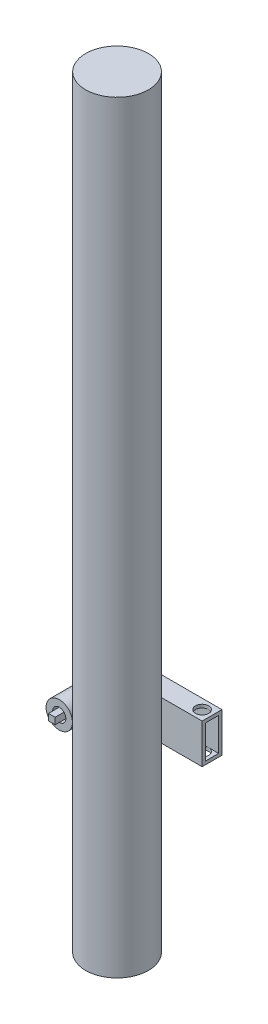
SolidWorks part; units mm, degrees
ref_plane "Front Plane" through (0, 0, 0) normal (0, 0, 1) x (1, 0, 0)
ref_plane "Top Plane" through (0, 0, 0) normal (0, 1, 0) x (1, 0, 0)
ref_plane "Right Plane" through (0, 0, 0) normal (1, 0, 0) x (0, 0, -1)
sketch "Elevation Bar" plane through (0, 0, 0) normal (0, 1, 0) x (1, 0, 0)
  circle A0 centre (0, 0) radius 30.226
  dimension "D1" = 60.452
extrude "Elevation Bar Part" add sketch "Elevation Bar" along normal blind 734.06
sketch "Pole and Drivetrain Pos" plane through (0, 0, 0) normal (0, 0, 1) x (1, 0, 0)
  line L0 (0, 0) -> (172.1794, 0) construction
  line L1 (-30.226, 0) -> (-30.226, 734.06) construction
  line L2 (-30.226, 734.06) -> (30.226, 734.06) construction
  line L3 (30.226, 734.06) -> (30.226, 0) construction
  line L4 (30.226, 0) -> (30.226, 734.06) construction
  line L5 (636.651, 40.7185) -> (27.051, 40.7185) construction
  line L6 (636.651, 53.4185) -> (27.051, 53.4185)
  line L7 (636.651, 53.4185) -> (636.651, 28.0185)
  line L8 (636.651, 28.0185) -> (27.051, 28.0185)
  line L9 (27.051, 53.4185) -> (27.051, 28.0185)
  line L10 (-30.226, 93.98) -> (30.226, 93.98) construction
  line L11 (33.2486, 0) -> (-33.2486, 0) construction
  line L12 (30.226, 185.42) -> (-30.226, 185.42) construction
  line L13 (30.226, 276.86) -> (-30.226, 276.86) construction
  line L14 (30.226, 368.3) -> (-30.226, 368.3) construction
  line L15 (30.226, 459.74) -> (-30.226, 459.74) construction
  line L16 (30.226, 551.18) -> (-30.226, 551.18) construction
  line L17 (30.226, 642.62) -> (-30.226, 642.62) construction
  line L18 (30.226, 73.152) -> (750.8896, 73.152) construction
  circle A0 centre (576.5632, 40.7185) radius 41.275 construction
  circle A1 centre (87.1388, 40.7185) radius 41.275 construction
  circle A2 centre (331.851, 40.7185) radius 41.275 construction
  point P24 (331.851, 40.7185)
  dimension "D2" = 82.55
  dimension "D1" = 609.6
  dimension "D3" = 25.4
  dimension "D4" = 244.7122
  dimension "D5" = 244.7122
  dimension "D6" = 93.98
  dimension "D7" = 185.42
  dimension "D8" = 276.86
  dimension "D9" = 368.3
  dimension "D10" = 459.74
  dimension "D11" = 551.18
  dimension "D12" = 642.62
  dimension "D13" = 73.152
sketch "Driving Wheels Geo" plane through (0, 0, 0) normal (0, 0, 1) x (1, 0, 0)
  line L0 (-30.226, 182.88) -> (-30.226, 101.727) construction
  line L1 (55.626, 101.727) -> (30.226, 101.727) construction
  line L2 (-30.226, 0) -> (-30.226, 734.06) construction
  line L3 (30.226, 734.06) -> (30.226, 0) construction
  line L5 (30.226, 101.727) -> (-30.226, 101.727) construction
  line L6 (-30.226, 182.88) -> (30.226, 101.727) construction
  line L7 (31.8135, 101.727) -> (-30.226, 182.88) construction
  line L8 (30.226, 226.8605) -> (203.668, 53.4185) construction
  line L9 (-42.926, 195.58) -> (44.3164, 195.58) construction
  line L10 (30.226, 73.152) -> (750.8896, 73.152) construction
  line L11 (636.651, 53.4185) -> (27.051, 53.4185) construction
  line L14 (-42.926, 170.18) -> (44.3164, 170.18) construction
  line L15 (44.3164, 170.18) -> (44.3164, 195.58) construction
  line L17 (31.6164, 195.58) -> (57.0164, 195.58) construction
  line L18 (31.6164, 195.58) -> (31.6164, 170.18) construction
  line L19 (31.6164, 170.18) -> (57.0164, 170.18) construction
  line L20 (57.0164, 195.58) -> (57.0164, 170.18) construction
  line L21 (31.6164, 195.58) -> (57.0164, 170.18) construction
  line L22 (31.6164, 170.18) -> (57.0164, 195.58) construction
  circle A1 centre (55.626, 101.727) radius 25.4
  circle A3 centre (-42.926, 182.88) radius 12.7
  circle A4 centre (81.026, 104.2185) radius 50.8 construction
  circle A5 centre (55.626, 101.727) radius 23.8125 construction
  point P28 (44.3164, 182.88)
  dimension "D1" = 50.8
  dimension "D2" = 1.5875
  dimension "D3" = 52.603
  dimension "D4" = 3.175
  dimension "D5" = 182.88
  dimension "D8" = 101.6
  dimension "D6" = 25.4
  dimension "D13" = 3.175
  dimension "D7" = 81.153
  dimension "D9" = 45
  dimension "D10" = 53.317
  dimension "D11" = 25.4
  dimension "D12" = 48.3085
ref_plane "Plane1" through (0, 182.88, 0) normal (0, 1, 0) x (1, 0, 0)
sketch "Clamp Geo" plane through (0, 182.88, 0) normal (0, 1, 0) x (1, 0, 0)
  line L0 (-42.926, -19.8438) -> (-42.926, 50.8635) construction
  line L3 (27.051, 228.6) -> (27.051, -228.6) construction
  line L4 (50.0464, 31.8135) -> (-49.276, 31.8135)
  line L5 (50.0464, 31.8135) -> (50.0464, 50.8635)
  line L6 (50.0464, 50.8635) -> (-49.276, 50.8635)
  line L7 (-49.276, 31.8135) -> (-49.276, 50.8635)
  line L10 (-46.101, 50.8635) -> (-39.751, 50.8635)
  line L11 (-46.101, 50.8635) -> (-46.101, -19.8438)
  line L12 (-46.101, -19.8438) -> (-39.751, -19.8438)
  line L13 (-39.751, 50.8635) -> (-39.751, -19.8438)
  line L14 (-55.626, 12.7) -> (-30.226, 12.7) construction
  line L15 (-55.626, 12.7) -> (-55.626, -12.7) construction
  line L16 (-55.626, -12.7) -> (-30.226, -12.7) construction
  line L17 (-30.226, 12.7) -> (-30.226, -12.7) construction
  line L18 (-55.626, 12.7) -> (-30.226, -12.7) construction
  line L19 (-55.626, -12.7) -> (-30.226, 12.7) construction
  line L20 (0, -30.226) -> (0, 30.226) construction
  line L21 (-30.226, 0) -> (30.226, 0) construction
  line L22 (-46.101, 46.101) -> (-42.926, 46.101) construction
  line L23 (-39.751, 41.3385) -> (-46.101, 41.3385)
  line L24 (-46.101, 41.3385) -> (-46.101, 50.8635) construction
  line L25 (-39.751, 31.8135) -> (-39.751, 50.8635) construction
  line L26 (50.0464, 41.3385) -> (40.5214, 41.3385) construction
  circle A0 centre (0, 0) radius 30.226 construction
  circle A3 centre (-42.926, 46.101) radius 1.8288
  circle A5 centre (-42.926, 36.576) radius 1.8288
  circle A6 centre (40.5214, 41.3385) radius 6.35
  circle A7 centre (40.5214, 41.3385) radius 13.4704 construction
  point P14 (-42.926, 0)
  point P32 (-39.751, 41.3385)
  point P34 (-46.101, 41.3385)
  point P36 (-42.926, 41.3385)
  point P42 (50.0464, 41.3385)
  dimension "D1" = 60.452
  dimension "D4" = 1.5875
  dimension "D7" = 3.6576
  dimension "D8" = 3.175
  dimension "D10" = 12.7
  dimension "D11" = 3.175
  dimension "D2" = 457.2
  dimension "D3" = 19.05
  dimension "D5" = 6.35
  dimension "D6" = 25.4
  dimension "D9" = 99.3224
  dimension "D13" = 7.1437
sketch "Locked Setting Geo" plane through (0, 182.88, 0) normal (0, 1, 0) x (1, 0, 0)
  line L0 (30.2525, 144.301) -> (91.1428, 108.3583) construction
  line L1 (27.477, 37.9778) -> (77.9656, 123.5104)
  line L2 (27.477, 37.9778) -> (43.8821, 28.2941)
  line L3 (43.8821, 28.2941) -> (94.3707, 113.8267)
  line L4 (77.9656, 123.5104) -> (94.3707, 113.8267)
  line L5 (92.7568, 111.0925) -> (89.5289, 105.6242)
  line L6 (92.7568, 111.0925) -> (31.8664, 147.0352)
  line L7 (31.8664, 147.0352) -> (28.6385, 141.5668)
  line L8 (89.5289, 105.6242) -> (28.6385, 141.5668)
  line L9 (64.7337, 138.6948) -> (51.8221, 116.8213) construction
  line L10 (64.7337, 138.6948) -> (42.8602, 151.6064) construction
  line L11 (42.8602, 151.6064) -> (29.9486, 129.7329) construction
  line L12 (51.8221, 116.8213) -> (29.9486, 129.7329) construction
  line L13 (64.7337, 138.6948) -> (29.9486, 129.7329) construction
  line L14 (42.8602, 151.6064) -> (51.8221, 116.8213) construction
  line L17 (88.6555, 113.5135) -> (87.0416, 110.7793) construction
  line L18 (81.3263, 110.466) -> (84.5542, 115.9344)
  line L19 (84.5542, 115.9344) -> (92.7568, 111.0925) construction
  line L20 (73.1238, 115.3079) -> (89.5289, 105.6242) construction
  line L21 (35.6795, 33.1359) -> (40.5214, 41.3385) construction
  line L22 (50.0464, 50.8635) -> (-49.276, 50.8635) construction
  line L23 (-46.101, 50.8635) -> (-46.101, -19.8438) construction
  line L24 (27.051, 228.6) -> (27.051, -228.6) construction
  circle A1 centre (87.0416, 110.7793) radius 1.8288
  circle A2 centre (78.839, 115.6211) radius 1.8288
  circle A3 centre (40.5214, 41.3385) radius 6.35
  point P10 (47.3411, 134.2138)
  point P28 (81.3263, 110.466)
  point P30 (84.5542, 115.9344)
  point P32 (82.9403, 113.2002)
  point P36 (35.6795, 33.1359)
  point P40 (40.5214, 41.3385)
  point P44 (-17.1792, 28.8062)
  dimension "D6" = 3.6576
  dimension "D9" = 12.7
  dimension "D2" = 19.05
  dimension "D3" = 1.5875
  dimension "D4" = 6.35
  dimension "D5" = 25.4
  dimension "D7" = 3.175
  dimension "D8" = 99.3224
  dimension "D10" = 3.175
  dimension "D11" = 50.8635
  dimension "D12" = 67.3197
extrude "Boss-Extrude1" add sketch "Clamp Geo" along normal blind 19.05 and the other way blind 19.05 separate body contours L6 L13 L4 L5 A6 | L11 L6 L7 L4 | L13 L23 L11 L4 A5 | L23 L13 L6 L11 A3 region at (2.3187, 182.88, -41.3385) region at (-42.926, 182.88, -31.928) region at (-47.6885, 182.88, -41.3385) region at (-42.926, 182.88, -41.453)
sketch "Sketch2" plane through (-49.276, 0, 0) normal (-1, 0, 0) x (0, 0, 1)
  line L0 (-41.3385, 201.93) -> (-41.3385, 163.83) construction
  line L1 (-31.8135, 201.93) -> (-50.8635, 201.93) construction
  line L2 (-31.8135, 163.83) -> (-50.8635, 163.83) construction
  line L3 (-31.8135, 163.83) -> (-31.8135, 201.93) construction
  line L4 (-47.6885, 167.005) -> (-34.9885, 167.005)
  line L5 (-47.6885, 167.005) -> (-47.6885, 198.755)
  line L6 (-47.6885, 198.755) -> (-34.9885, 198.755)
  line L7 (-34.9885, 167.005) -> (-34.9885, 198.755)
  line L8 (-47.6885, 167.005) -> (-34.9885, 198.755) construction
  line L9 (-47.6885, 198.755) -> (-34.9885, 167.005) construction
  point P6 (-41.3385, 182.88)
  dimension "D1" = 3.175
  dimension "D2" = 3.175
extrude "Cut-Extrude2" cut sketch "Sketch2" against normal up to surface (99.3224 mm away) up to face at (50.0464, 182.88, -41.3385)
sketch "Sketch3" plane through (0, 0, -50.8635) normal (0, 0, -1) x (-1, 0, 0)
  line L2 (39.7129, 179.6669) -> (46.1391, 179.6669)
  line L3 (39.7129, 179.6669) -> (39.7129, 186.0931)
  line L4 (39.7129, 186.0931) -> (46.1391, 186.0931)
  line L5 (46.1391, 179.6669) -> (46.1391, 186.0931)
  line L6 (39.7129, 179.6669) -> (46.1391, 186.0931) construction
  line L7 (39.7129, 186.0931) -> (46.1391, 179.6669) construction
  point P0 (42.926, 182.88)
  point P1 (42.926, 182.88)
  dimension "D1" = 6.4262
extrude "Cut-Extrude3" cut sketch "Sketch3" against normal up to surface (19.05 mm away) up to face at (0.3852, 182.88, -31.8135)
extrude "Boss-Extrude2" add sketch "Clamp Geo<3>" along normal blind 3.175 and the other way blind 3.175 separate body contours L13 L4 L11 L12 | L13 L23 L11 L4 A5 | L23 L13 L6 L11 A3 region at (-42.926, 182.88, -5.9849) region at (-42.926, 182.88, -31.928) region at (-42.926, 182.88, -41.453)
sketch "Clamp Geo<3>" plane through (0, 182.88, 0) normal (0, 1, 0) x (1, 0, 0) same geometry as "Clamp Geo"
sketch "Custom Driven Flywheel" plane through (0, 0, 0) normal (0, 0, 1) x (1, 0, 0)
  circle A0 centre (-42.926, 182.88) radius 12.7 construction
  circle A1 centre (-42.926, 182.88) radius 12.7
  circle A2 centre (-42.926, 182.88) radius 6.35
  dimension "D1" = 12.7
extrude "Boss-Extrude3" add sketch "Custom Driven Flywheel" along normal mid plane 25.4 separate body
sketch "Sketch8" plane through (0, 167.005, 0) normal (0, 1, 0) x (1, 0, 0)
  line L0 (-42.926, 47.6885) -> (-42.926, 34.9885) construction
  line L1 (-49.276, 34.9885) -> (-36.576, 34.9885) construction
  line L2 (-49.276, 34.9885) -> (-49.276, 47.6885)
  line L3 (-49.276, 47.6885) -> (-36.576, 47.6885) construction
  line L4 (-36.576, 34.9885) -> (-36.576, 47.6885)
  line L5 (-36.576, 41.3385) -> (-42.926, 41.3385) construction
  line L6 (-42.926, 41.3385) -> (-49.276, 41.3385) construction
  line L7 (-43.8339, 34.9885) -> (-49.276, 34.9885)
  line L8 (-43.8339, 47.6885) -> (-49.276, 47.6885)
  line L9 (-42.0181, 34.9885) -> (-36.576, 34.9885)
  line L10 (-42.0181, 47.6885) -> (-36.576, 47.6885)
  arc A0 (-43.8339, 47.6885) -> (-42.0181, 47.6885) centre (-42.926, 46.101) ccw construction
  arc A2 (-42.0181, 34.9885) -> (-43.8339, 34.9885) centre (-42.926, 36.576) ccw construction
  arc A3 (-43.8339, 47.6885) -> (-42.0181, 47.6885) centre (-42.926, 46.101) ccw
  arc A4 (-42.0181, 34.9885) -> (-43.8339, 34.9885) centre (-42.926, 36.576) ccw
extrude "Boss-Extrude5" add sketch "Sketch8" along normal up to surface (15.875 mm away) separate body up to plane "Plane1"
sketch "Sketch10" plane through (0, 182.88, 0) normal (0, 1, 0) x (1, 0, 0)
  line L0 (-36.576, 41.3385) -> (-49.276, 41.3385) construction
  line L1 (-36.576, 34.9885) -> (-36.576, 47.6885) construction
  line L2 (-49.276, 47.6885) -> (-49.276, 34.9885) construction
  line L3 (-49.276, 34.9885) -> (-43.8339, 34.9885) construction
  line L4 (-46.1391, 34.9885) -> (-39.7129, 34.9885)
  line L5 (-46.1391, 34.9885) -> (-46.1391, 47.6885)
  line L6 (-46.1391, 47.6885) -> (-39.7129, 47.6885)
  line L7 (-39.7129, 34.9885) -> (-39.7129, 47.6885)
  line L8 (-46.1391, 34.9885) -> (-39.7129, 47.6885) construction
  line L9 (-46.1391, 47.6885) -> (-39.7129, 34.9885) construction
  point P6 (-42.926, 41.3385)
  point P11 (0, 0)
  dimension "D1" = 6.4262
extrude "Cut-Extrude5" cut sketch "Sketch10" against normal blind 6.3881
equation "\"D5@Pole and Drivetrain Pos\" = \"D4@Pole and Drivetrain Pos\""
